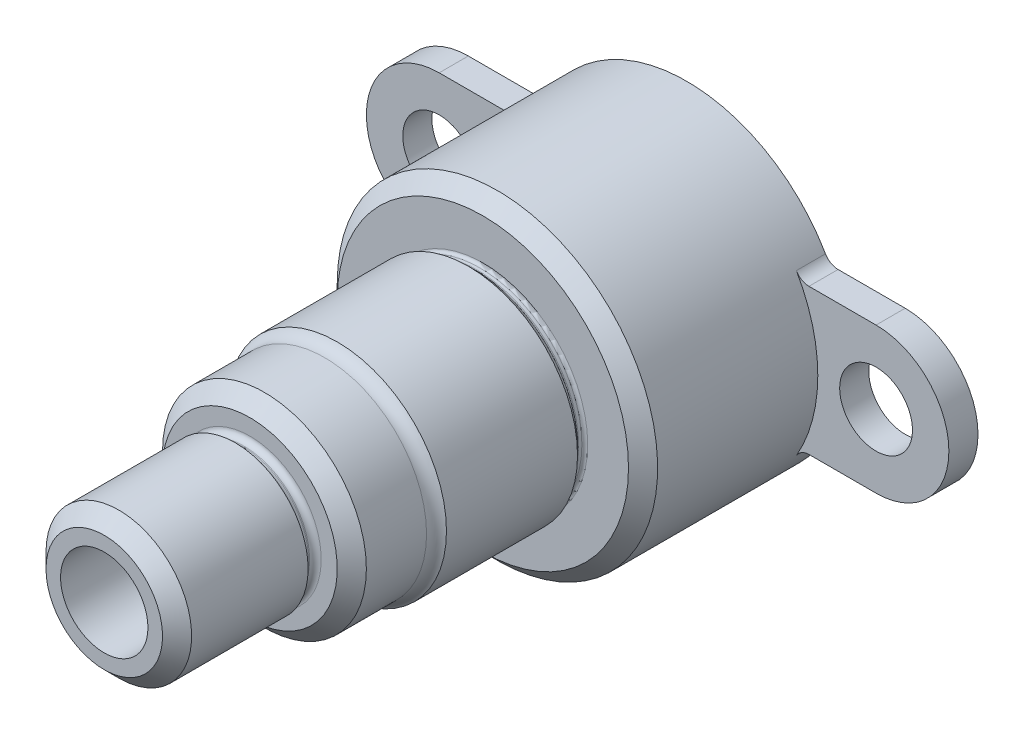
SolidWorks part; units mm, degrees
ref_plane "Спереди" through (0, 0, 0) normal (0, 0, 1) x (1, 0, 0)
ref_plane "Сверху" through (0, 0, 0) normal (0, 1, 0) x (1, 0, 0)
ref_plane "Справа" through (0, 0, 0) normal (1, 0, 0) x (0, 0, -1)
sketch "Эскиз1" plane through (0, 0, 0) normal (1, 0, 0) x (0, 0, -1)
  line L0 (-28.643, 0) -> (42.3762, 0) construction
  line L1 (30, 11) -> (16, 11)
  line L2 (30, 10) -> (25, 10)
  line L3 (30, 11) -> (30, 10)
  line L4 (18, 8) -> (25, 8)
  line L5 (25, 8) -> (25, 10)
  line L6 (-10, 5) -> (0, 5)
  line L7 (-10, 3) -> (2, 3)
  line L10 (-10, 3) -> (-10, 5)
  line L11 (2, 3) -> (2, 6)
  line L12 (2, 6) -> (18, 6)
  line L13 (18, 6) -> (18, 8)
  line L14 (0, 5) -> (0, 7.5)
  line L15 (0, 7.5) -> (16, 7.5)
  line L16 (16, 7.5) -> (16, 11)
  point P12 (15.8409, 11)
  dimension "D1" = 40
  dimension "D2" = 22
  dimension "D3" = 20
  dimension "D4" = 2
  dimension "D5" = 5
  dimension "D6" = 10
  dimension "D7" = 6
  dimension "D8" = 10
  dimension "D9" = 14
  dimension "D10" = 2
  dimension "D11" = 2
  dimension "D12" = 1.5
  dimension "D13" = 15
revolve "Повернуть1" add sketch "Эскиз1" angle 360 about L0
sketch "Эскиз2" plane through (0, 0, 0) normal (0, 1, 0) x (1, 0, 0)
  line L0 (4.5, 0) -> (5, 0)
  line L1 (5, 0) -> (5, -1)
  line L2 (5, -10) -> (5, 0) construction
  line L4 (4.5, -0.7) -> (4.5, 0)
  line L5 (0, 0) -> (0, -7.3244) construction
  line L6 (5, -1) -> (4.5, -0.7)
  dimension "D1" = 0.5
  dimension "D2" = 1
  dimension "D3" = 0.7
revolve "Вырез-Повернуть1" cut sketch "Эскиз2" angle 360 about L5
fillet "Скругление1" radius 0.4 2 edges at (-4.5, 0, 0) (-4.5, 0, 0.7)
sketch "Эскиз3" plane through (0, 0, 0) normal (0, 1, 0) x (1, 0, 0)
  line L0 (0, 0) -> (0, 36.5873) construction
  line L1 (-10, 25) -> (-10.2236, 25)
  line L2 (-10.2236, 25) -> (-10.2236, 25.5)
  line L4 (-10, 25.7) -> (-10, 25)
  line L7 (-10.2236, 25.5) -> (-10, 25.7)
  line L8 (-10, 30) -> (-10, 25) construction
  dimension "D1" = 0.3
  dimension "D2" = 0.5
  dimension "D3" = 0.7
revolve "Вырез-Повернуть2" cut sketch "Эскиз3" angle 360 about L0
fillet "Скругление2" radius 0.2 2 edges at (10.2236, 0, -25.5) (10.2236, 0, -25)
sketch "Эскиз4" plane through (0, 0, -30) normal (0, 0, -1) x (-1, 0, 0)
  line L0 (-22.9294, 0) -> (20.459, 0) construction
  line L1 (-15, 5) -> (-9.798, 5)
  line L2 (-15, -5) -> (-9.798, -5)
  arc A0 (-9.798, 5) -> (-9.798, -5) centre (0, 0) ccw
  circle A1 centre (0, 0) radius 11 construction
  arc A2 (-15, 5) -> (-15, -5) centre (-15, 0) ccw
  dimension "D1" = 15
  dimension "D2" = 5
extrude "Бобышка-Вытянуть1" add sketch "Эскиз4" against normal blind 2
hole_wizard "Диаметр отверстия Ø5.0 (5)1" positions "Эскиз5" profile "Эскиз6" hole size "Ø5.0" standard "Ansi Metric" end condition through all
sketch "Эскиз5" plane through (0, 0, -30) normal (0, 0, -1) x (-1, 0, 0)
  point P0 (-15, 0)
sketch "Эскиз6" plane through (15, 0, -30) normal (1, 0, 0) x (0, 1, 0)
  line L0 (0, 0) -> (0, 40)
  line L1 (0, 40) -> (2.5, 40)
  line L2 (2.5, 40) -> (2.5, 0)
  line L5 (2.5, 0) -> (0, 0)
  line L11 (0, -6.35) -> (0, 107.95) construction
  dimension "Диаметр сквозного отверстия" = 5
  dimension "Глубина сквозного отверстия" = 40
mirror "Зеркальное отражение1" about plane through (0, 0, 0) normal (1, 0, 0) of "Бобышка-Вытянуть1", "Диаметр отверстия Ø5.0 (5)1"
chamfer "Фаска2" distance 0.5 angle 45 1 edges at (10, 0, -30)
fillet "Скругление4" radius 1 4 edges at (-9.798, -5, -29) (-9.798, 5, -29) (9.798, -5, -29) (9.798, 5, -29)
chamfer "Фаска1" distance 1 angle 45 2 edges at (5, 0, 10) (8, 0, -25)
sketch "Эскиз7" plane through (0, 0, 0) normal (1, 0, 0) x (0, 0, -1)
  line L0 (0, 7.5) -> (6, 7.5)
  line L1 (6, 7.5) -> (6, 7)
  line L2 (6, 7) -> (0, 7)
  line L3 (0, 7) -> (0, 7.5)
  line L4 (0, 0) -> (18.304, 0) construction
  point P8 (0.0937, 11.5221)
  point P9 (0.3639, 7.0005)
  dimension "D1" = 6
  dimension "D2" = 14
revolve "Вырез-Повернуть3" cut sketch "Эскиз7" angle 360 about L4
cosmetic thread "Условное изображение резьбы1" parameters "D2"=12.344
fillet "Скругление5" radius 1 1 edges at (7, 0, -6)
chamfer "Фаска3" distance 1 angle 45 1 edges at (7, 0, 0)
sketch "Эскиз8" plane through (0, 0, 0) normal (1, 0, 0) x (0, 0, -1)
  line L0 (0, 0) -> (38.2899, 0) construction
  line L1 (15.8, 7) -> (15.5828, 7)
  line L3 (16, 7.2) -> (16, 7.5)
  line L4 (16, 7.5) -> (15, 7.5)
  line L5 (15, 7.5) -> (15.4414, 7.0586)
  arc A0 (15.4414, 7.0586) -> (15.5828, 7) centre (15.5828, 7.2) ccw
  arc A1 (15.8, 7) -> (16, 7.2) centre (15.8, 7.2) ccw
  point P5 (18.3782, 7.3488)
  point P7 (17.864, 7.5214)
  point P8 (18.3609, 7)
  dimension "D4" = 0.2
  dimension "D1" = 0.5
  dimension "D2" = 1
  dimension "D3" = 45
revolve "Вырез-Повернуть4" cut sketch "Эскиз8" angle 360 about L0
chamfer "Фаска4" distance 1 angle 45 1 edges at (11, 0, -16)
fillet "Скругление6" radius 1 1 edges at (6, 0, -2)
